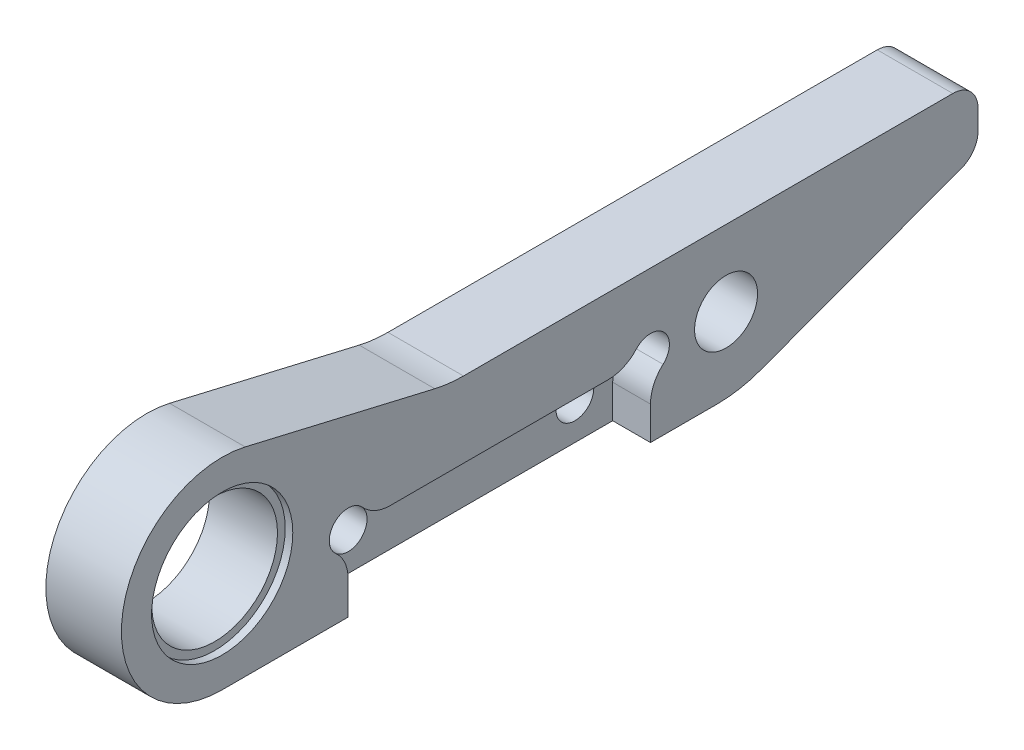
SolidWorks part; units mm, degrees
material "1060 Alloy"
ref_plane "Front Plane" through (0, 0, 0) normal (0, 0, 1) x (1, 0, 0)
ref_plane "Top Plane" through (0, 0, 0) normal (0, 1, 0) x (1, 0, 0)
ref_plane "Right Plane" through (0, 0, 0) normal (1, 0, 0) x (0, 0, -1)
sketch "Sketch27" plane through (0, 0, 0) normal (1, 0, 0) x (0, 0, -1)
  line L0 (50, 46) -> (28, 46)
  line L1 (28, 46) -> (11.8246, 49.7891)
  line L2 (50, 46) -> (70, 46)
  line L3 (10, 42) -> (31.9317, 42) construction
  line L4 (31.9317, 42) -> (31.9317, 54) construction
  line L5 (50, 34) -> (51.074, 34)
  line L6 (10, 34) -> (50, 34)
  line L7 (31.9317, 54) -> (10, 42) construction
  line L8 (0, 0) -> (60, 0) construction
  line L9 (0, 0) -> (0, 58) construction
  line L10 (0, 58) -> (60, 58) construction
  line L11 (60, 0) -> (60, 58) construction
  line L12 (70, 46) -> (70, 41)
  line L13 (51.074, 34) -> (70, 41)
  arc A0 (11.8246, 49.7891) -> (10, 34) centre (10, 42) ccw
  circle A3 centre (10, 42) radius 5.6 construction
  arc A4 (50, 46) -> (50, 34) centre (50, 40) cw construction
  circle A5 centre (10, 42) radius 4.99
  circle A6 centre (50, 40) radius 2.5
  dimension "D9" = 6
  dimension "D10" = 5
  dimension "D11" = 22
  dimension "D12" = 9.98
  dimension "D13" = 8
  dimension "D14" = 5
  dimension "D6" = 20
  dimension "D16" = 11.2
  dimension "D1" = 60
  dimension "D2" = 58
  dimension "D3" = 42
  dimension "D4" = 10
  dimension "D5" = 50
  dimension "D7" = 40
  dimension "D8" = 12
  dimension "D17" = 25
extrude "Boss-Extrude1" add sketch "Sketch27" along normal blind 6
sketch "Sketch33" plane through (6, 0, 0) normal (1, 0, 0) x (0, 0, -1)
  circle A0 centre (10, 42) radius 5.605
  dimension "D1" = 11.21
extrude "Cut-Extrude2" cut sketch "Sketch33" against normal blind 0.6
sketch "Sketch34" plane through (6, 0, 0) normal (1, 0, 0) x (0, 0, -1)
  line L0 (20, 34) -> (44, 34)
  line L1 (20, 34) -> (20, 40)
  line L2 (44, 34) -> (44, 40)
  line L3 (20, 40) -> (44, 40)
  line L4 (10, 34) -> (51.074, 34) construction
  circle A0 centre (50, 40) radius 2.5 construction
  dimension "D1" = 24
  dimension "D2" = 6
  dimension "D3" = 6
extrude "Cut-Extrude3" cut sketch "Sketch34" against normal blind 3
sketch "Sketch35" plane through (6, 0, 0) normal (1, 0, 0) x (0, 0, -1)
  circle A0 centre (20, 40) radius 1.5
  circle A1 centre (44, 40) radius 1.5
  dimension "D1" = 3
extrude "Cut-Extrude4" cut sketch "Sketch35" against normal up to surface (3 mm away) up to face at (3, 37, -32)
fillet "Fillet1" radius 3 4 edges at (4.5, 38.5, -44) (4.5, 40, -42.5) (4.5, 38.5, -20) (4.5, 40, -21.5)
sketch "Sketch36" plane through (3, 0, 0) normal (1, 0, 0) x (0, 0, -1)
  line L0 (20, 36.6459) -> (20, 34) construction
  line L1 (20, 34) -> (44, 34) construction
  line L2 (44, 34) -> (44, 36.6459) construction
  circle A0 centre (23, 37) radius 1.5
  circle A1 centre (41, 37) radius 1.5
  dimension "D1" = 3
  dimension "D2" = 3
  dimension "D3" = 3
  dimension "D4" = 3
  dimension "D5" = 3
extrude "Cut-Extrude5" cut sketch "Sketch36" against normal up to next
fillet "Fillet2" radius 10 1 edges at (3, 46, -28)
fillet "Fillet3" radius 2 2 edges at (3, 46, -70) (3, 41, -70)
fillet "Fillet4" radius 10 1 edges at (3, 34, -51.074)
